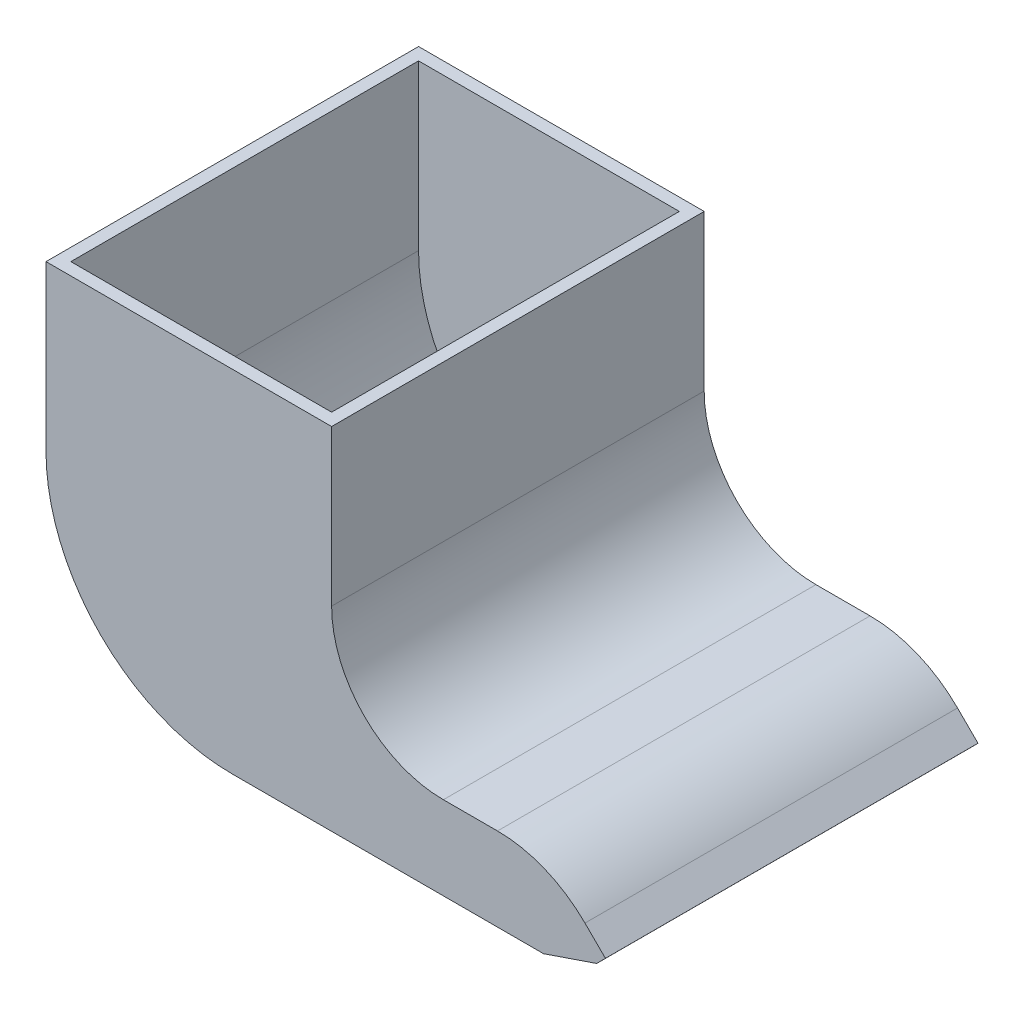
SolidWorks part; units mm, degrees
ref_plane "Front Plane" through (0, 0, 0) normal (0, 0, 1) x (1, 0, 0)
ref_plane "Top Plane" through (0, 0, 0) normal (0, 1, 0) x (1, 0, 0)
ref_plane "Right Plane" through (0, 0, 0) normal (1, 0, 0) x (0, 0, -1)
sketch "Sketch1" plane through (0, 0, 0) normal (0, 0, 1) x (1, 0, 0)
  line L0 (0, 0) -> (0, -9.942)
  line L1 (0, -9.942) -> (0, -13.2322)
  line L2 (15, -28.2322) -> (40.0648, -28.2322)
  line L3 (22, 0) -> (22, -9.942)
  line L5 (40.0648, -22.5257) -> (44.3448, -26.7735)
  line L6 (40.0648, -22.5257) -> (32, -22.5257)
  line L7 (22, -9.942) -> (22, -12.5257)
  arc A0 (0, -13.2322) -> (15, -28.2322) centre (15, -13.2322) ccw
  arc A1 (32, -22.5257) -> (22, -12.5257) centre (32, -12.5257) cw
  dimension "D2" = 15
  dimension "D3" = 10
  dimension "D1" = 22
extrude "Extrude-Thin1" add sketch "Sketch1" along normal blind 30 thin thin type one direction reverse wall 1
ref_plane "Plane1" through (0, 0, 30) normal (0, 0, 1) x (1, 0, 0)
sketch "Sketch2" plane through (0, 0, 30) normal (0, 0, 1) x (1, 0, 0)
  line L1 (44.3448, -26.7735) -> (45.0492, -26.0637) construction
  line L2 (45.0492, -26.0637) -> (40.4768, -21.5257) construction
  line L4 (23, -12.5257) -> (23, 0) construction
  line L5 (23, 0) -> (22, 0) construction
  line L8 (15, -28.2322) -> (40.0648, -28.2322) construction
  line L9 (40.0648, -28.2322) -> (40.0648, -27.2322) construction
  line L12 (1, 0) -> (0, 0) construction
  line L13 (0, 0) -> (0, -13.2322) construction
  line L14 (32, -21.5257) -> (40.4768, -21.5257)
  line L15 (44.3448, -26.7735) -> (45.0492, -26.0637)
  line L16 (45.0492, -26.0637) -> (40.4768, -21.5257)
  line L18 (23, -12.5257) -> (23, 0)
  line L19 (23, 0) -> (22, 0)
  line L22 (15, -28.2322) -> (40.0648, -28.2322)
  line L23 (40.0648, -28.2322) -> (40.0648, -27.2322)
  line L26 (1, 0) -> (0, 0)
  line L27 (0, 0) -> (0, -13.2322)
  line L28 (1, 0) -> (22, 0)
  line L29 (40.0648, -28.2322) -> (44.3448, -26.7735)
  arc A1 (0, -13.2322) -> (15, -28.2322) centre (15, -13.2322) ccw construction
  arc A2 (23, -12.5257) -> (32, -21.5257) centre (32, -12.5257) ccw
  arc A3 (0, -13.2322) -> (15, -28.2322) centre (15, -13.2322) ccw
  point P12 (0, 0)
  point P13 (32, -12.5257)
  point P19 (28.9407, -15.585)
extrude "Boss-Extrude1" add sketch "Sketch2" against normal blind 1 contours L27 A3 L22 L29 L15 L16 L18 L19 L28 L26 region at (16.139, -15.4648, 30)
ref_plane "Plane2" through (-0.3287, -0.2669, 14.4649) normal (0.0227, 0.0184, -0.9996) x (-0.9997, 0.0004, -0.0227)
sketch "Sketch3" plane through (0, 0, 0) normal (0, 0, -1) x (-1, 0, 0)
  line L0 (-40.0648, -28.2322) -> (-15, -28.2322) construction
  line L1 (0, -13.2322) -> (0, 0) construction
  line L2 (0, 0) -> (-1, 0) construction
  line L3 (-1, 0) -> (-1, -13.2322) construction
  line L5 (-40.0648, -27.2322) -> (-40.0648, -28.2322) construction
  line L7 (-40.0648, -22.5257) -> (-32, -22.5257) construction
  line L8 (-22, -12.5257) -> (-22, 0) construction
  line L9 (-22, 0) -> (-23, 0) construction
  line L10 (-23, 0) -> (-23, -12.5257) construction
  line L11 (-32, -21.5257) -> (-40.4768, -21.5257) construction
  line L12 (-40.4768, -21.5257) -> (-45.0492, -26.0637) construction
  line L13 (-45.0492, -26.0637) -> (-44.3448, -26.7735) construction
  line L14 (-40.0648, -28.2322) -> (-15, -28.2322)
  line L15 (0, -13.2322) -> (0, 0)
  line L16 (0, 0) -> (-1, 0)
  line L17 (-1, 0) -> (-1, -13.2322)
  line L19 (-40.0648, -27.2322) -> (-40.0648, -28.2322)
  line L21 (-40.0648, -22.5257) -> (-32, -22.5257)
  line L22 (-22, -12.5257) -> (-22, 0)
  line L23 (-22, 0) -> (-23, 0)
  line L24 (-23, 0) -> (-23, -12.5257)
  line L25 (-32, -21.5257) -> (-40.4768, -21.5257)
  line L26 (-40.4768, -21.5257) -> (-45.0492, -26.0637)
  line L27 (-45.0492, -26.0637) -> (-44.3448, -26.7735)
  line L28 (-1, 0) -> (-22, 0)
  line L29 (-40.0648, -28.2322) -> (-44.3448, -26.7735)
  arc A0 (-15, -28.2322) -> (0, -13.2322) centre (-15, -13.2322) ccw construction
  arc A1 (-15, -27.2322) -> (-1, -13.2322) centre (-15, -13.2322) ccw construction
  arc A2 (-32, -22.5257) -> (-22, -12.5257) centre (-32, -12.5257) ccw construction
  arc A3 (-32, -21.5257) -> (-23, -12.5257) centre (-32, -12.5257) ccw construction
  arc A4 (-15, -28.2322) -> (0, -13.2322) centre (-15, -13.2322) ccw
  arc A5 (-15, -27.2322) -> (-1, -13.2322) centre (-15, -13.2322) ccw
  arc A6 (-32, -22.5257) -> (-22, -12.5257) centre (-32, -12.5257) ccw
  arc A7 (-32, -21.5257) -> (-23, -12.5257) centre (-32, -12.5257) ccw
extrude "Boss-Extrude2" add sketch "Sketch3" against normal blind 1 contours L14 A4 L15 L16 L28 L29 region at (15.3558, -15.4084, 0)
fillet "Fillet1" radius 10 2 edges at (40.4768, -21.5257, 15) (40.0648, -22.5257, 15)
fillet "Fillet2" radius 5 1 edges at (40.0648, -27.2322, 15)
